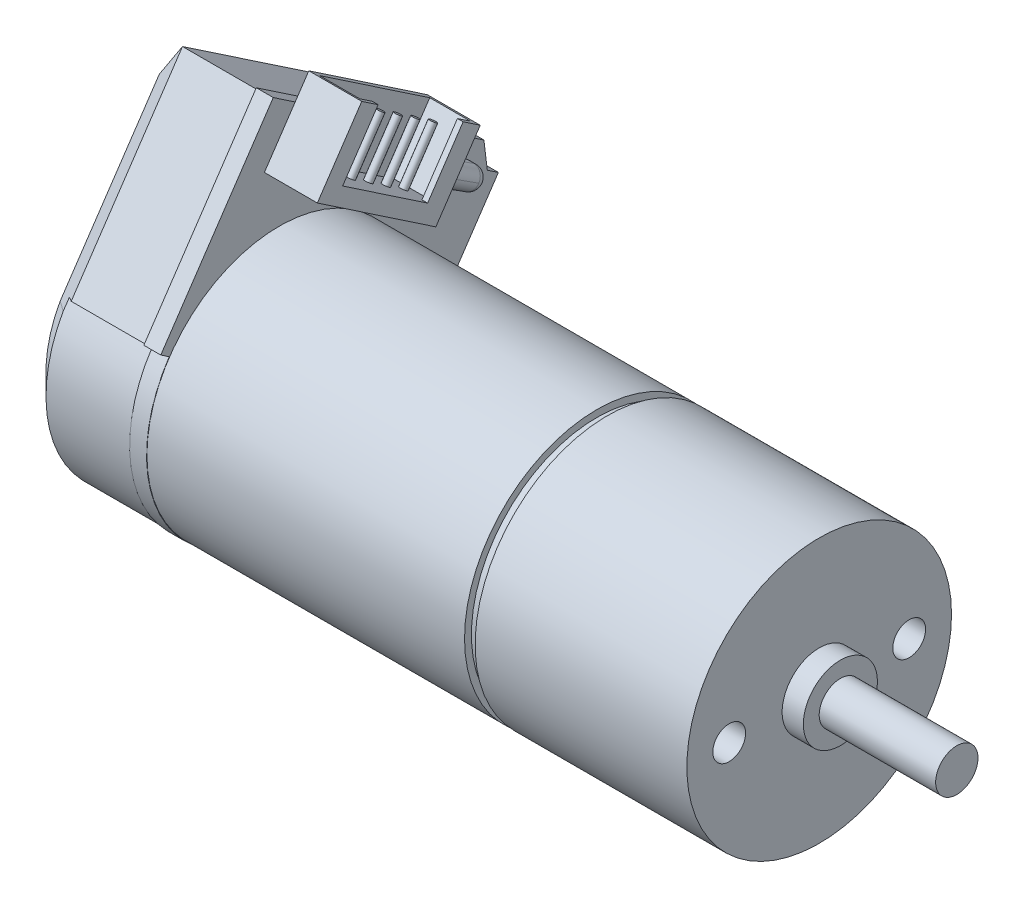
SolidWorks part; units mm, degrees
ref_plane "Front Plane" through (0, 0, 0) normal (0, 0, 1) x (1, 0, 0)
ref_plane "Top Plane" through (0, 0, 0) normal (0, 1, 0) x (1, 0, 0)
ref_plane "Right Plane" through (0, 0, 0) normal (1, 0, 0) x (0, 0, -1)
sketch "Sketch1" plane through (0, 0, 0) normal (1, 0, 0) x (0, 0, -1)
  circle A0 centre (0, 0) radius 12.5
extrude "Boss-Extrude1" add sketch "Sketch1" along normal blind 30
sketch "Sketch2" plane through (30, 0, 0) normal (1, 0, 0) x (0, 0, -1)
  circle A0 centre (0, 0) radius 11.8497
extrude "Boss-Extrude2" add sketch "Sketch2" along normal blind 1
sketch "Sketch3" plane through (31, 0, 0) normal (1, 0, 0) x (0, 0, -1)
  circle A0 centre (0, 0) radius 12.5
extrude "Boss-Extrude3" add sketch "Sketch3" along normal blind 20
sketch "Sketch4" plane through (51, 0, 0) normal (1, 0, 0) x (0, 0, -1)
  circle A1 centre (-8.5, 0) radius 1.55
  circle A2 centre (8.5, 0) radius 1.55
  dimension "D1" = 8.5
  dimension "D2" = 8.5
extrude "Cut-Extrude1" cut sketch "Sketch4" against normal blind 5
sketch "Sketch5" plane through (51, 0, 0) normal (1, 0, 0) x (0, 0, -1)
  circle A0 centre (0, 0) radius 3.5
extrude "Boss-Extrude4" add sketch "Sketch5" along normal blind 2
sketch "Sketch6" plane through (53, 0, 0) normal (1, 0, 0) x (0, 0, -1)
  circle A0 centre (0, 0) radius 2
extrude "Boss-Extrude5" add sketch "Sketch6" along normal blind 11
sketch "Sketch7" plane through (0, 0, 0) normal (-1, 0, 0) x (0, 0, 1)
  circle A0 centre (0, 0) radius 12.0162
extrude "Cut-Extrude2" cut sketch "Sketch7" against normal blind 2
sketch "Sketch8" plane through (2, 0, 0) normal (-1, 0, 0) x (0, 0, 1)
  line L1 (-0.2423, 10) -> (-0.7423, 10)
  line L2 (-0.2423, 10) -> (-0.2423, 8)
  line L3 (-0.2423, 8) -> (-0.7423, 8)
  line L4 (-0.7423, 10) -> (-0.7423, 8)
  line L5 (0.5, -8) -> (0, -8)
  line L6 (0.5, -8) -> (0.5, -10)
  line L7 (0.5, -10) -> (0, -10)
  line L8 (0, -8) -> (0, -10)
  dimension "D1" = 0.5
  dimension "D2" = 0.5
  dimension "D3" = 2
  dimension "D4" = 2
  dimension "D5" = 8
  dimension "D6" = 8
extrude "Boss-Extrude6" add sketch "Sketch8" along normal blind 4
sketch "Sketch9" plane through (0, 0, -0.2423) normal (0, 0, 1) x (1, 0, 0)
  circle A0 centre (-0.7284, 9.0582) radius 0.56
extrude "Cut-Extrude3" cut sketch "Sketch9" against normal up to next
sketch "Sketch10" plane through (0, 0, 0.5) normal (0, 0, 1) x (1, 0, 0)
  circle A0 centre (-1.0044, -8.968) radius 0.5203
extrude "Cut-Extrude4" cut sketch "Sketch10" against normal up to next
sketch "Sketch11" plane through (2, 0, 0) normal (-1, 0, 0) x (0, 0, 1)
  circle A0 centre (0, 0) radius 3.5
extrude "Boss-Extrude7" add sketch "Sketch11" along normal blind 2
sketch "Sketch12" plane through (0, 0, 0) normal (-1, 0, 0) x (0, 0, 1)
  line L0 (11.192, 7.5491) -> (-11.192, -7.5491) construction
  line L1 (0, 0) -> (13.5, 0) construction
  line L2 (11.192, 7.5491) -> (10.392, 7.0095)
  line L3 (11.192, 7.5491) -> (0.5673, 23.3008)
  line L4 (-11.192, -7.5491) -> (-20.6983, 6.5445)
  line L5 (0.5673, 23.3008) -> (-19.3296, 9.8802)
  line L6 (11.192, 7.5491) -> (10.392, 7.0095)
  line L7 (10.392, 7.0095) -> (10.3126, 6.956)
  line L8 (-11.192, -7.5491) -> (-10.392, -7.0095)
  line L9 (-10.392, -7.0095) -> (-11.192, -7.5491)
  line L10 (-19.3296, 9.8802) -> (-19.6506, 7.2512)
  line L11 (-19.6506, 7.2512) -> (-20.6983, 6.5445)
  arc A0 (-10.392, -7.0095) -> (10.392, 7.0095) centre (0, 0) ccw
  dimension "D4" = 12.535
  dimension "D1" = 34
  dimension "D2" = 19
  dimension "D3" = 27
  dimension "D5" = 2
  dimension "D6" = 3
extrude "Boss-Extrude8" add sketch "Sketch12" along normal blind 1.6
sketch "Sketch14" plane through (-1.6, 0, 0) normal (-1, 0, 0) x (0, 0, 1)
  line L14 (-11.165, -7.4103) -> (-10.3647, -6.8704)
  line L15 (10.2528, 7.0362) -> (11.0532, 7.5761)
  line L16 (11.0532, 7.5761) -> (0.5404, 23.162)
  line L17 (0.5404, 23.162) -> (-19.2358, 9.8228)
  line L18 (-19.2358, 9.8228) -> (-19.5569, 7.1938)
  line L19 (-19.5569, 7.1938) -> (-20.5595, 6.5176)
  line L20 (-20.5595, 6.5176) -> (-11.165, -7.4103)
  line L21 (-11.165, -7.4103) -> (-10.3647, -6.8704)
  line L22 (10.2528, 7.0362) -> (11.0532, 7.5761)
  line L23 (11.0532, 7.5761) -> (0.5404, 23.162)
  line L24 (0.5404, 23.162) -> (-19.2358, 9.8228)
  line L25 (-19.2358, 9.8228) -> (-19.5569, 7.1938)
  line L26 (-19.5569, 7.1938) -> (-20.5595, 6.5176)
  line L27 (-20.5595, 6.5176) -> (-11.165, -7.4103)
  arc A2 (-10.3647, -6.8704) -> (10.2528, 7.0362) centre (0, 0) ccw
  arc A3 (-10.3647, -6.8704) -> (10.2528, 7.0362) centre (0, 0) ccw
  dimension "D1" = 0.1
extrude "Boss-Extrude9" add sketch "Sketch14" along normal blind 10
chamfer "Chamfer1" distance 3 angle 45 3 edges at (-11.6, -0.4464, -15.8622) (-11.6, 15.369, 5.7968) (-11.6, 16.4924, -9.3477)
sketch "Sketch15" plane through (-11.6, 0, 0) normal (-1, 0, 0) x (0, 0, 1)
  line L0 (-4.0846, 4.4358) -> (-1.988, 2.5711)
  line L1 (-4.0846, 4.4358) -> (-4.8821, 3.5391)
  line L2 (4.8821, -3.5391) -> (4.0846, -4.4358)
  line L3 (-4.8821, 3.5391) -> (-2.7855, 1.6744)
  line L4 (1.988, -2.5711) -> (4.0846, -4.4358)
  line L5 (2.7855, -1.6744) -> (4.8821, -3.5391)
  arc A0 (2.7855, -1.6744) -> (-1.988, 2.5711) centre (0, 0) ccw
  arc A1 (-2.7855, 1.6744) -> (1.988, -2.5711) centre (0, 0) ccw
  circle A2 centre (0, 0) radius 2.5
  dimension "D1" = 5
  dimension "D4" = 6.5
  dimension "D2" = 12
  dimension "D3" = 1.2
  dimension "D5" = 2.8059
extrude "Boss-Extrude10" add sketch "Sketch15" along normal blind 1.6
chamfer "Chamfer2" distance 1.5 angle 60 2 edges at (-13.2, -3.9874, 4.4833) (-13.2, 3.9874, -4.4833) first distance on face at (-12.4, -3.9874, 4.4833) first distance on face at (-12.4, 3.9874, -4.4833)
sketch "Sketch16" plane through (0, 0, 0) normal (1, 0, 0) x (0, 0, -1)
  line L0 (2.7914, 23.8096) -> (-1.4026, 17.5918)
  line L1 (2.7914, 23.8096) -> (13.9834, 16.2605)
  line L2 (-1.4026, 17.5918) -> (9.7895, 10.0427)
  line L3 (13.9834, 16.2605) -> (9.7895, 10.0427)
  line L4 (-11.192, 7.5491) -> (-0.5673, 23.3008) construction
  line L5 (-0.5673, 23.3008) -> (19.3296, 9.8802) construction
  dimension "D1" = 7.5
  dimension "D2" = 13.5
  dimension "D3" = 2.5
  dimension "D4" = 2.3
extrude "Boss-Extrude11" add sketch "Sketch16" along normal blind 5
sketch "Sketch17" plane through (0, 17.6585, -11.9108) normal (0, 0.829, -0.5592) x (1, 0, 0)
  line L0 (4.4628, 0.5506) -> (4.4628, 1.997)
  line L1 (4.4628, 1.997) -> (0.6459, 1.997)
  line L2 (0.6459, 1.997) -> (0.6459, -10.5787)
  line L3 (0.6459, -10.5787) -> (4.4628, -10.5787)
  line L4 (4.4628, -10.5787) -> (4.4628, -9.1323)
  line L5 (4.4628, -9.1323) -> (5.3065, -9.1323)
  line L6 (5.3065, -9.1323) -> (5.3065, 0.5506)
  line L7 (5.3065, 0.5506) -> (4.4628, 0.5506)
extrude "Cut-Extrude5" cut sketch "Sketch17" against normal blind 6
sketch "Sketch18" plane through (0, 0, 0) normal (1, 0, 0) x (0, 0, -1)
  line L0 (12.9448, 10.99) -> (17.1507, 8.2862) construction
  line L1 (13.4855, 11.8311) -> (17.6914, 9.1274)
  line L2 (12.404, 10.1488) -> (16.6099, 7.445)
  arc A0 (13.4855, 11.8311) -> (12.404, 10.1488) centre (12.9448, 10.99) ccw
  arc A1 (16.6099, 7.445) -> (17.6914, 9.1274) centre (17.1507, 8.2862) ccw
  point P2 (15.0477, 9.6381)
  dimension "D2" = 1
  dimension "D1" = 5
extrude "Boss-Extrude12" add sketch "Sketch18" along normal blind 1.7
fillet "Fillet3" radius 1 4 edges at (1.7, 10.4792, -15.5885) (1.7, 7.7454, -17.9918) (1.7, 8.7969, -14.507) (1.7, 11.5307, -12.1036)
sketch "Sketch19" plane through (0, 12.6843, -8.5557) normal (0, 0.829, -0.5592) x (1, 0, 0)
  circle A0 centre (2.6135, 0.6718) radius 0.3491
  circle A1 centre (2.6135, -1.3282) radius 0.3491
  circle A2 centre (2.6135, -3.3282) radius 0.3491
  circle A3 centre (2.6135, -5.3282) radius 0.3491
  circle A4 centre (2.6135, -7.3282) radius 0.3491
  circle A5 centre (2.6135, -9.3282) radius 0.3491
  dimension "D1" = 6
extrude "Boss-Extrude13" add sketch "Sketch19" along normal blind 5
chamfer "Chamfer3" distance 2 angle 45 1 edges at (-11.6, -10.3091, 6.9536)
